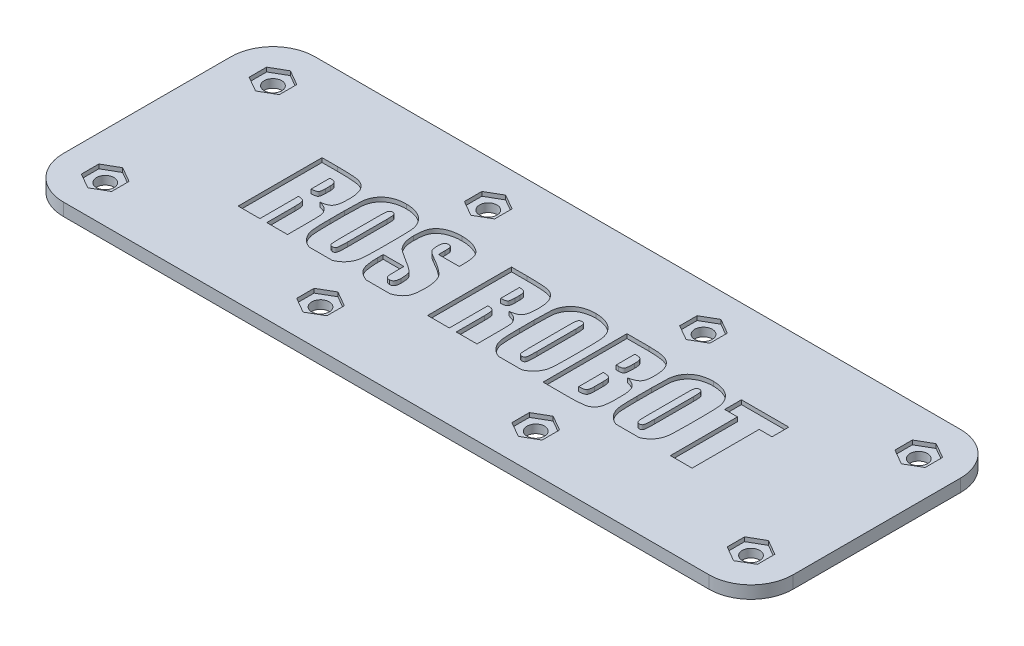
SolidWorks part; units mm, degrees
ref_plane "Front Plane" through (0, 0, 0) normal (0, 0, 1) x (1, 0, 0)
ref_plane "Top Plane" through (0, 0, 0) normal (0, 1, 0) x (1, 0, 0)
ref_plane "Right Plane" through (0, 0, 0) normal (1, 0, 0) x (0, 0, -1)
sketch "Sketch1" plane through (0, 0, 0) normal (0, 1, 0) x (1, 0, 0)
  line L1 (-87, 30) -> (87, 30)
  line L2 (-87, 30) -> (-87, -30)
  line L3 (-87, -30) -> (87, -30)
  line L4 (87, 30) -> (87, -30)
  line L5 (-87, 30) -> (87, -30) construction
  line L6 (-87, -30) -> (87, 30) construction
  point P0 (0, 0)
  dimension "D1" = 60
  dimension "D2" = 174
extrude "Boss-Extrude1" add sketch "Sketch1" along normal blind 3
sketch "Sketch2" plane through (0, 3, 0) normal (0, 1, 0) x (1, 0, 0)
  line L0 (-87, 30) -> (-87, -30) construction
  circle A0 centre (-76.995, 20) radius 2.09
  circle A1 centre (-25.665, 20) radius 2.09
  circle A2 centre (25.665, 20) radius 2.09
  circle A3 centre (76.995, 20) radius 2.09
  dimension "D1" = 4.18
  dimension "D2" = 4
  dimension "D3" = 10.005
  dimension "D4" = 20
extrude "Cut-Extrude1" cut sketch "Sketch2" against normal through all
mirror "Mirror1" about plane through (0, 0, 0) normal (0, 0, 1) of "Cut-Extrude1"
fillet "Fillet1" radius 10 4 edges at (-87, 1.5, 30) (87, 1.5, 30) (87, 1.5, -30) (-87, 1.5, -30)
sketch "Sketch3" plane through (0, 3, 0) normal (0, 1, 0) x (1, 0, 0)
  line L0 (-70, -10) -> (70, -10)
  line L1 (-55.2941, 10) -> (-51.5662, 10)
  line L2 (-43.5294, -4.6581) -> (-43.5294, -10)
  line L3 (-43.5294, -10) -> (-48.4706, -10)
  line L4 (-48.4706, -10) -> (-48.4706, -3.2353)
  line L5 (-50.1176, -0.8235) -> (-50.1176, -10)
  line L6 (-50.1176, -10) -> (-55.2941, -10)
  line L7 (-55.2941, -10) -> (-55.2941, 10)
  line L8 (-50.1176, 6.7059) -> (-50.1176, 2.2353)
  line L9 (-48.4706, 4.0478) -> (-48.4706, 5.1544)
  line L10 (-41.6471, -1.7206) -> (-41.6471, 1.7206)
  line L11 (-29.6471, 1.7206) -> (-29.6471, -1.7206)
  line L12 (-36.4706, 4.9596) -> (-36.4706, -4.5662)
  line L13 (-34.8235, -4.4154) -> (-34.8235, 4.9596)
  line L14 (-16.4706, 3.8824) -> (-21.4118, 3.8824)
  line L15 (-21.4118, 3.8824) -> (-21.4118, 5.4632)
  line L16 (-28, -4.0478) -> (-28, -2.7059)
  line L17 (-28, -2.7059) -> (-23.0588, -2.7059)
  line L18 (-23.0588, -2.7059) -> (-23.0588, -5.2978)
  line L19 (-16.4706, 4.6875) -> (-16.4706, 3.8824)
  line L20 (-10.1176, 10) -> (-6.3897, 10)
  line L21 (1.6471, -4.6581) -> (1.6471, -10)
  line L22 (1.6471, -10) -> (-3.2941, -10)
  line L23 (-3.2941, -10) -> (-3.2941, -3.2353)
  line L24 (-4.9412, -0.8235) -> (-4.9412, -10)
  line L25 (-4.9412, -10) -> (-10.1176, -10)
  line L26 (-10.1176, -10) -> (-10.1176, 10)
  line L27 (-4.9412, 6.7059) -> (-4.9412, 2.2353)
  line L28 (-3.2941, 4.0478) -> (-3.2941, 5.1544)
  line L29 (3.5294, -1.7206) -> (3.5294, 1.7206)
  line L30 (15.5294, 1.7206) -> (15.5294, -1.7206)
  line L31 (8.7059, 4.9596) -> (8.7059, -4.5662)
  line L32 (10.3529, -4.4154) -> (10.3529, 4.9596)
  line L33 (17.4118, 10) -> (22.7169, 10)
  line L34 (29.6471, -3.364) -> (29.6471, -5.2426)
  line L35 (23.4926, -10) -> (17.4118, -10)
  line L36 (17.4118, -10) -> (17.4118, 10)
  line L37 (22.5882, 6.7059) -> (22.5882, 2.2353)
  line L38 (22.5882, -0.8235) -> (22.5882, -6.7059)
  line L39 (24.4706, -4.7463) -> (24.4706, -2.7831)
  line L40 (31.5294, -1.7206) -> (31.5294, 1.7206)
  line L41 (43.5294, 1.7206) -> (43.5294, -1.7206)
  line L42 (36.7059, 4.9596) -> (36.7059, -4.5662)
  line L43 (38.3529, -4.4154) -> (38.3529, 4.9596)
  line L44 (56, 10) -> (56, 6)
  line L45 (56, 6) -> (52.9412, 6)
  line L46 (52.9412, 6) -> (52.9412, -10)
  line L47 (52.9412, -10) -> (47.7647, -10)
  line L48 (47.7647, -10) -> (47.7647, 6)
  line L49 (47.7647, 6) -> (44.7059, 6)
  line L50 (44.7059, 6) -> (44.7059, 10)
  line L51 (44.7059, 10) -> (56, 10)
  spline S0 degree 3 poles (-51.5662, 10) (-50.9938, 10.0021) (-50.1738, 9.9925) (-49.131, 9.9618) (-48.4616, 9.9343) (-47.8671, 9.8938) (-47.3485, 9.8469) (-46.9053, 9.7938) (-46.5265, 9.7279) (-46.1927, 9.6422) (-45.8846, 9.5296) (-45.5898, 9.3956) (-45.3117, 9.2282) (-45.0523, 9.0316) (-44.8023, 8.8156) (-44.5748, 8.5646) (-44.3559, 8.2904) (-44.158, 7.9777) (-43.9907, 7.6226) (-43.847, 7.2263) (-43.7305, 6.7869) (-43.6403, 6.3051) (-43.5478, 5.579) (-43.5348, 5.0099) (-43.5294, 4.6176) knots 0 0 0 0 0.148881 0.213303 0.271377 0.323138 0.368276 0.406827 0.439217 0.468212 0.496346 0.524443 0.552325 0.580569 0.609028 0.638128 0.668547 0.700209 0.734143 0.770448 0.80973 0.852244 0.897872 1 1 1 1
  spline S1 degree 3 poles (-43.5294, 4.6176) (-43.5236, 4.2653) (-43.5474, 3.7599) (-43.6025, 3.1182) (-43.671, 2.7076) (-43.7489, 2.3431) (-43.8469, 2.023) (-43.9667, 1.7514) (-44.1058, 1.5209) (-44.2744, 1.3269) (-44.4747, 1.1564) (-44.7132, 1.0108) (-44.9842, 0.8814) (-45.2896, 0.7718) (-45.7649, 0.6509) (-46.1435, 0.5949) (-46.4081, 0.5735) knots 0 0 0 0 0.18379 0.264137 0.336087 0.400976 0.458649 0.510492 0.555595 0.598692 0.64408 0.692369 0.744168 0.800637 0.861472 1 1 1 1
  spline S2 degree 3 poles (-46.4081, 0.5735) (-46.1692, 0.5082) (-45.8228, 0.4157) (-45.3924, 0.2537) (-45.1176, 0.1239) (-44.8709, -0.0075) (-44.6579, -0.1504) (-44.475, -0.3016) (-44.2801, -0.5089) (-44.0843, -0.7699) (-43.8891, -1.0747) (-43.748, -1.3697) (-43.6652, -1.6199) (-43.6287, -1.8463) (-43.5978, -2.0715) (-43.5791, -2.3577) (-43.5604, -2.7033) (-43.5466, -3.1078) (-43.5296, -3.7658) (-43.5348, -4.2893) (-43.5294, -4.6581) knots 0 0 0 0 0.11023 0.159227 0.204341 0.24532 0.283418 0.318243 0.350629 0.40972 0.463107 0.511383 0.554826 0.57974 0.613275 0.655917 0.707227 0.767226 0.835926 1 1 1 1
  spline S3 degree 3 poles (-48.4706, -3.2353) (-48.4728, -2.9891) (-48.4724, -2.639) (-48.5052, -2.1981) (-48.5325, -1.9256) (-48.5697, -1.6913) (-48.6105, -1.4957) (-48.6657, -1.339) (-48.7289, -1.2146) (-48.8113, -1.114) (-48.9232, -1.039) (-49.055, -0.9678) (-49.2166, -0.9133) (-49.4044, -0.8752) (-49.7069, -0.834) (-49.9484, -0.8249) (-50.1176, -0.8235) knots 0 0 0 0 0.208712 0.296135 0.374434 0.440653 0.497065 0.543362 0.580978 0.614872 0.652041 0.694298 0.741574 0.795735 0.856514 1 1 1 1
  spline S4 degree 3 poles (-50.1176, 2.2353) (-49.8576, 2.2338) (-49.4959, 2.2542) (-49.0697, 2.3585) (-48.8674, 2.4456) (-48.7457, 2.5571) (-48.6674, 2.6702) (-48.6082, 2.8204) (-48.5571, 3.0015) (-48.5182, 3.2158) (-48.4758, 3.5672) (-48.4762, 3.8494) (-48.4706, 4.0478) knots 0 0 0 0 0.26319 0.361521 0.442778 0.481273 0.526535 0.580255 0.643242 0.716208 0.799609 1 1 1 1
  spline S5 degree 3 poles (-48.4706, 5.1544) (-48.4732, 5.4183) (-48.4915, 5.7882) (-48.649, 6.209) (-48.8134, 6.422) (-49.0502, 6.5523) (-49.4796, 6.6913) (-49.8538, 6.7008) (-50.1176, 6.7059) knots 0 0 0 0 0.296724 0.405999 0.497474 0.590179 0.702697 1 1 1 1
  spline S6 degree 3 poles (-29.6471, -1.7206) (-29.6515, -2.1875) (-29.649, -2.8616) (-29.6628, -3.7232) (-29.6839, -4.2868) (-29.699, -4.7944) (-29.7259, -5.2478) (-29.7546, -5.6462) (-29.7961, -6.1016) (-29.8819, -6.6249) (-30.0686, -7.2195) (-30.3331, -7.7852) (-30.6652, -8.3214) (-31.0707, -8.8126) (-31.5464, -9.2461) (-32.0877, -9.6199) (-32.694, -9.9286) (-33.3578, -10.1686) (-34.3389, -10.4147) (-35.1174, -10.4641) (-35.6471, -10.4706) knots 0 0 0 0 0.112809 0.162854 0.208179 0.249065 0.285542 0.317902 0.345566 0.396043 0.445676 0.495616 0.546553 0.597656 0.649001 0.701564 0.75612 0.812885 0.871769 1 1 1 1
  spline S7 degree 3 poles (-35.6471, -10.4706) (-36.157, -10.4718) (-36.9063, -10.4086) (-37.8652, -10.1914) (-38.5237, -9.9594) (-39.1336, -9.6653) (-39.6789, -9.2941) (-40.1716, -8.8683) (-40.5862, -8.3693) (-40.9353, -7.8326) (-41.2061, -7.2648) (-41.3995, -6.6755) (-41.4957, -6.1587) (-41.5357, -5.7074) (-41.565, -5.3091) (-41.59, -4.8519) (-41.6129, -4.3384) (-41.6259, -3.766) (-41.6415, -2.8873) (-41.6458, -2.1985) (-41.6471, -1.7206) knots 0 0 0 0 0.123179 0.180929 0.237119 0.291548 0.344027 0.396062 0.448383 0.50021 0.550408 0.599943 0.649656 0.677029 0.709392 0.746168 0.787661 0.833574 0.884513 1 1 1 1
  spline S8 degree 3 poles (-41.6471, 1.7206) (-41.6425, 2.1887) (-41.6454, 2.8628) (-41.6311, 3.7244) (-41.6108, 4.2868) (-41.5934, 4.7954) (-41.5734, 5.2491) (-41.5426, 5.6473) (-41.5025, 6.102) (-41.4109, 6.6245) (-41.2257, 7.2194) (-40.9622, 7.7848) (-40.6264, 8.3182) (-40.225, 8.8141) (-39.7442, 9.2434) (-39.2063, 9.6217) (-38.599, 9.9269) (-37.9368, 10.1755) (-36.9518, 10.4071) (-36.1771, 10.476) (-35.6471, 10.4706) knots 0 0 0 0 0.1131 0.162847 0.20817 0.249054 0.28581 0.317873 0.345536 0.396062 0.445693 0.495631 0.546315 0.597643 0.649205 0.701523 0.756077 0.812942 0.872041 1 1 1 1
  spline S9 degree 3 poles (-35.6471, 10.4706) (-35.1376, 10.4697) (-34.3878, 10.4128) (-33.4319, 10.1862) (-32.7748, 9.9554) (-32.1629, 9.6647) (-31.6159, 9.2964) (-31.1263, 8.8668) (-30.7111, 8.3696) (-30.3634, 7.8316) (-30.0871, 7.2658) (-29.8946, 6.6743) (-29.798, 6.1563) (-29.7599, 5.7048) (-29.7225, 5.3082) (-29.7063, 4.8517) (-29.6803, 4.3385) (-29.6698, 3.7659) (-29.6434, 2.8875) (-29.6546, 2.1984) (-29.6471, 1.7206) knots 0 0 0 0 0.123202 0.180743 0.236944 0.291253 0.343988 0.395811 0.448142 0.499979 0.550314 0.59986 0.649873 0.677251 0.709348 0.746116 0.787617 0.833538 0.884493 1 1 1 1
  spline S10 degree 3 poles (-34.8235, 4.9596) (-34.8242, 5.1753) (-34.83, 5.4829) (-34.843, 5.8716) (-34.8622, 6.1155) (-34.8839, 6.3276) (-34.9074, 6.5086) (-34.9406, 6.6559) (-34.9862, 6.806) (-35.0702, 6.954) (-35.2687, 7.1431) (-35.486, 7.1725) (-35.6213, 7.1765) knots 0 0 0 0 0.245382 0.350014 0.44228 0.523563 0.592561 0.649714 0.69512 0.770679 0.840726 1 1 1 1
  spline S11 degree 3 poles (-35.6213, 7.1765) (-35.7476, 7.1828) (-35.9326, 7.1386) (-36.1407, 7.0007) (-36.2446, 6.8771) (-36.3135, 6.7446) (-36.354, 6.6034) (-36.3908, 6.4253) (-36.4175, 6.2075) (-36.4453, 5.9516) (-36.4612, 5.5307) (-36.473, 5.1963) (-36.4706, 4.9596) knots 0 0 0 0 0.141273 0.207934 0.278501 0.320511 0.375555 0.443281 0.525523 0.622695 0.733336 1 1 1 1
  spline S12 degree 3 poles (-36.4706, -4.5662) (-36.4661, -4.8346) (-36.4689, -5.2158) (-36.4552, -5.6951) (-36.4341, -5.9902) (-36.4194, -6.2432) (-36.3928, -6.4541) (-36.365, -6.6225) (-36.3252, -6.7864) (-36.2427, -6.9456) (-36.032, -7.1431) (-35.8027, -7.1757) (-35.6581, -7.1765) knots 0 0 0 0 0.263966 0.37491 0.47152 0.554902 0.624119 0.680394 0.722784 0.789642 0.853612 1 1 1 1
  spline S13 degree 3 poles (-35.6581, -7.1765) (-35.5065, -7.1791) (-35.2706, -7.1295) (-35.0575, -6.9077) (-34.9787, -6.7275) (-34.9317, -6.5458) (-34.9057, -6.3632) (-34.8796, -6.1401) (-34.8574, -5.8753) (-34.8447, -5.5687) (-34.8286, -5.0773) (-34.825, -4.6887) (-34.8235, -4.4154) knots 0 0 0 0 0.145036 0.209347 0.281953 0.327187 0.385478 0.455017 0.538188 0.634996 0.743262 1 1 1 1
  spline S14 degree 3 poles (-21.4118, 5.4632) (-21.4127, 5.7647) (-21.4197, 6.1714) (-21.5052, 6.6431) (-21.5927, 6.8638) (-21.7193, 7.0116) (-21.938, 7.1462) (-22.1365, 7.1803) (-22.2721, 7.1765) knots 0 0 0 0 0.412843 0.553103 0.65361 0.73318 0.814494 1 1 1 1
  spline S15 degree 3 poles (-22.2721, 7.1765) (-22.4224, 7.1753) (-22.6526, 7.1339) (-22.8986, 6.9564) (-23.0494, 6.7779) (-23.1638, 6.5473) (-23.267, 6.1427) (-23.3007, 5.8109) (-23.2941, 5.5735) knots 0 0 0 0 0.212113 0.312859 0.418563 0.535756 0.66915 1 1 1 1
  spline S16 degree 3 poles (-23.2941, 5.5735) (-23.2963, 5.2685) (-23.2666, 4.7355) (-23.1434, 4.2139) (-23.0441, 4.0074) knots 0 0 0 0 0.572651 1 1 1 1
  spline S17 degree 3 poles (-23.0441, 4.0074) (-22.9953, 3.9087) (-22.892, 3.7635) (-22.7165, 3.5783) (-22.5391, 3.4317) (-22.3344, 3.2741) (-21.9996, 3.0492) (-21.7223, 2.8928) (-21.5294, 2.7831) knots 0 0 0 0 0.166753 0.269572 0.387216 0.516182 0.662459 1 1 1 1
  spline S18 degree 3 poles (-21.5294, 2.7831) (-20.9703, 2.4734) (-20.1729, 2.0184) (-19.1897, 1.3881) (-18.5738, 0.9563) (-18.0389, 0.5522) (-17.4805, 0.0677) (-17.1194, -0.3024) (-16.9375, -0.5662) knots 0 0 0 0 0.335278 0.4813 0.612364 0.729739 0.832713 1 1 1 1
  spline S19 degree 3 poles (-16.9375, -0.5662) (-16.77, -0.806) (-16.5589, -1.2115) (-16.3573, -1.8106) (-16.226, -2.3243) (-16.1237, -2.8906) (-16.0244, -3.7446) (-16, -4.4137) (-16, -4.875) knots 0 0 0 0 0.195997 0.304678 0.423526 0.551406 0.690506 1 1 1 1
  spline S20 degree 3 poles (-16, -4.875) (-15.998, -5.2123) (-16.0141, -5.701) (-16.0695, -6.3269) (-16.1225, -6.7434) (-16.1969, -7.1236) (-16.2837, -7.469) (-16.3859, -7.7809) (-16.5079, -8.061) (-16.6548, -8.3173) (-16.8301, -8.5575) (-17.0323, -8.7896) (-17.2656, -9.0103) (-17.5281, -9.2213) (-17.8225, -9.4176) (-18.1454, -9.6065) (-18.6171, -9.8482) (-19.2609, -10.0984) (-20.3935, -10.3986) (-21.2929, -10.4667) (-21.9044, -10.4706) knots 0 0 0 0 0.107307 0.155459 0.199907 0.240819 0.278648 0.313174 0.345124 0.37569 0.406967 0.439576 0.4735 0.509002 0.546638 0.58596 0.627987 0.715167 0.805112 1 1 1 1
  spline S21 degree 3 poles (-21.9044, -10.4706) (-22.2484, -10.4757) (-22.7548, -10.4446) (-23.4141, -10.3628) (-23.8804, -10.2732) (-24.328, -10.1612) (-24.7555, -10.0192) (-25.1658, -9.8605) (-25.5494, -9.6676) (-25.9093, -9.4591) (-26.2396, -9.2368) (-26.5368, -8.9991) (-26.8027, -8.7496) (-27.0363, -8.4842) (-27.2339, -8.2027) (-27.4071, -7.9126) (-27.5395, -7.5995) (-27.6487, -7.2653) (-27.7465, -6.9026) (-27.8193, -6.5061) (-27.8876, -6.0774) (-27.9373, -5.6159) (-27.9879, -4.936) (-27.9998, -4.4094) (-28, -4.0478) knots 0 0 0 0 0.100145 0.147666 0.193464 0.238409 0.281993 0.324627 0.366464 0.406944 0.445764 0.482345 0.517706 0.551866 0.585155 0.617796 0.650099 0.683973 0.720175 0.759459 0.801374 0.84664 0.894618 1 1 1 1
  spline S22 degree 3 poles (-23.0588, -5.2978) (-23.0613, -5.4794) (-23.049, -5.7378) (-23.0335, -6.0657) (-23.0047, -6.2711) (-22.98, -6.4517) (-22.9371, -6.6031) (-22.8953, -6.7301) (-22.8277, -6.8628) (-22.7117, -6.9937) (-22.4544, -7.1506) (-22.2151, -7.1729) (-22.0551, -7.1765) knots 0 0 0 0 0.221449 0.31586 0.400263 0.474516 0.538003 0.591926 0.637412 0.719013 0.801608 1 1 1 1
  spline S23 degree 3 poles (-22.0551, -7.1765) (-21.8855, -7.181) (-21.6369, -7.1297) (-21.3606, -6.9481) (-21.2049, -6.755) (-21.0818, -6.5138) (-20.9682, -6.0948) (-20.9412, -5.7502) (-20.9412, -5.5074) knots 0 0 0 0 0.223296 0.324627 0.430189 0.546596 0.679609 1 1 1 1
  spline S24 degree 3 poles (-20.9412, -5.5074) (-20.9409, -5.2301) (-20.9533, -4.8334) (-21.0013, -4.3304) (-21.0575, -4.013) (-21.1206, -3.7324) (-21.2279, -3.4321) (-21.3302, -3.2311) (-21.4228, -3.125) knots 0 0 0 0 0.336674 0.481824 0.613234 0.728042 0.830673 1 1 1 1
  spline S25 degree 3 poles (-21.4228, -3.125) (-21.528, -3.0068) (-21.7234, -2.8316) (-22.0286, -2.599) (-22.3207, -2.3816) (-22.6652, -2.1468) (-23.2182, -1.7846) (-23.6661, -1.5149) (-23.9779, -1.3235) knots 0 0 0 0 0.151175 0.250667 0.367276 0.49971 0.649705 1 1 1 1
  spline S26 degree 3 poles (-23.9779, -1.3235) (-24.2945, -1.1313) (-24.7469, -0.8536) (-25.3157, -0.487) (-25.6766, -0.2459) (-25.9964, -0.028) (-26.2707, 0.1697) (-26.5041, 0.3453) (-26.7572, 0.5568) (-27.0307, 0.8386) (-27.3222, 1.2196) (-27.5825, 1.6572) (-27.8168, 2.1499) (-28.0109, 2.7079) (-28.187, 3.5918) (-28.2419, 4.2954) (-28.2353, 4.7868) knots 0 0 0 0 0.139497 0.199929 0.25485 0.30299 0.345648 0.382207 0.412998 0.469794 0.529711 0.593278 0.661207 0.734924 0.815133 1 1 1 1
  spline S27 degree 3 poles (-28.2353, 4.7868) (-28.2299, 5.1483) (-28.2229, 5.6721) (-28.1555, 6.342) (-28.0911, 6.7866) (-28.0062, 7.1929) (-27.9063, 7.5618) (-27.7803, 7.8893) (-27.6392, 8.183) (-27.4744, 8.4486) (-27.2854, 8.6932) (-27.0793, 8.9296) (-26.8428, 9.1431) (-26.5869, 9.3479) (-26.3089, 9.5388) (-26.0053, 9.711) (-25.5665, 9.9259) (-24.9651, 10.1466) (-23.8851, 10.4114) (-23.0241, 10.4702) (-22.4338, 10.4706) knots 0 0 0 0 0.115094 0.16642 0.214115 0.25793 0.298418 0.335563 0.369391 0.401957 0.434786 0.46765 0.501588 0.535991 0.571894 0.608743 0.64693 0.727243 0.81197 1 1 1 1
  spline S28 degree 3 poles (-22.4338, 10.4706) (-22.0994, 10.4657) (-21.6053, 10.4579) (-20.9648, 10.377) (-20.5106, 10.312) (-20.0772, 10.2133) (-19.6613, 10.1018) (-19.2659, 9.965) (-18.8924, 9.8068) (-18.5432, 9.6352) (-18.2193, 9.4575) (-17.9337, 9.2583) (-17.6686, 9.0613) (-17.4461, 8.8391) (-17.2428, 8.617) (-17.0786, 8.377) (-16.9405, 8.1223) (-16.8309, 7.8384) (-16.7307, 7.5198) (-16.6529, 7.1549) (-16.5815, 6.7482) (-16.5328, 6.2949) (-16.4819, 5.6039) (-16.471, 5.0626) (-16.4706, 4.6875) knots 0 0 0 0 0.103081 0.151694 0.198641 0.244219 0.288419 0.331125 0.37288 0.413199 0.450863 0.486435 0.520313 0.552325 0.583055 0.612876 0.641566 0.672036 0.706398 0.744284 0.786764 0.83346 0.884523 1 1 1 1
  spline S29 degree 3 poles (-6.3897, 10) (-5.8173, 10.0021) (-4.9973, 9.9925) (-3.9545, 9.9618) (-3.2851, 9.9343) (-2.6907, 9.8938) (-2.172, 9.8469) (-1.7288, 9.7938) (-1.3501, 9.7279) (-1.0162, 9.6422) (-0.7081, 9.5296) (-0.4133, 9.3956) (-0.1353, 9.2282) (0.1241, 9.0316) (0.3741, 8.8156) (0.6016, 8.5646) (0.8205, 8.2904) (1.0184, 7.9777) (1.1858, 7.6226) (1.3294, 7.2263) (1.4459, 6.7869) (1.5362, 6.3051) (1.6287, 5.579) (1.6416, 5.0099) (1.6471, 4.6176) knots 0 0 0 0 0.148881 0.213303 0.271377 0.323138 0.368276 0.406827 0.439217 0.468212 0.496346 0.524443 0.552325 0.580569 0.609028 0.638128 0.668547 0.700209 0.734143 0.770448 0.80973 0.852244 0.897872 1 1 1 1
  spline S30 degree 3 poles (1.6471, 4.6176) (1.6529, 4.2653) (1.629, 3.7599) (1.574, 3.1182) (1.5054, 2.7076) (1.4275, 2.3431) (1.3296, 2.023) (1.2098, 1.7514) (1.0707, 1.5209) (0.9021, 1.3269) (0.7018, 1.1564) (0.4633, 1.0108) (0.1923, 0.8814) (-0.1131, 0.7718) (-0.5885, 0.6509) (-0.9671, 0.5949) (-1.2316, 0.5735) knots 0 0 0 0 0.18379 0.264137 0.336087 0.400976 0.458649 0.510492 0.555595 0.598692 0.64408 0.692369 0.744168 0.800637 0.861472 1 1 1 1
  spline S31 degree 3 poles (-1.2316, 0.5735) (-0.9927, 0.5082) (-0.6463, 0.4157) (-0.2159, 0.2537) (0.0589, 0.1239) (0.3056, -0.0075) (0.5186, -0.1504) (0.7015, -0.3016) (0.8963, -0.5089) (1.0921, -0.7699) (1.2873, -1.0747) (1.4284, -1.3697) (1.5113, -1.6199) (1.5478, -1.8463) (1.5787, -2.0715) (1.5973, -2.3577) (1.6161, -2.7033) (1.6298, -3.1078) (1.6469, -3.7658) (1.6416, -4.2893) (1.6471, -4.6581) knots 0 0 0 0 0.11023 0.159227 0.204341 0.24532 0.283418 0.318243 0.350629 0.40972 0.463107 0.511383 0.554826 0.57974 0.613275 0.655917 0.707227 0.767226 0.835926 1 1 1 1
  spline S32 degree 3 poles (-3.2941, -3.2353) (-3.2963, -2.9891) (-3.2959, -2.639) (-3.3287, -2.1981) (-3.356, -1.9256) (-3.3932, -1.6913) (-3.434, -1.4957) (-3.4893, -1.339) (-3.5525, -1.2146) (-3.6348, -1.114) (-3.7468, -1.039) (-3.8785, -0.9678) (-4.0401, -0.9133) (-4.2279, -0.8752) (-4.5304, -0.834) (-4.7719, -0.8249) (-4.9412, -0.8235) knots 0 0 0 0 0.208712 0.296135 0.374434 0.440653 0.497065 0.543362 0.580978 0.614872 0.652041 0.694298 0.741574 0.795735 0.856514 1 1 1 1
  spline S33 degree 3 poles (-4.9412, 2.2353) (-4.6811, 2.2338) (-4.3195, 2.2542) (-3.8932, 2.3585) (-3.691, 2.4456) (-3.5692, 2.5571) (-3.491, 2.6702) (-3.4317, 2.8204) (-3.3807, 3.0015) (-3.3417, 3.2158) (-3.2993, 3.5672) (-3.2997, 3.8494) (-3.2941, 4.0478) knots 0 0 0 0 0.26319 0.361521 0.442778 0.481273 0.526535 0.580255 0.643242 0.716208 0.799609 1 1 1 1
  spline S34 degree 3 poles (-3.2941, 5.1544) (-3.2968, 5.4183) (-3.315, 5.7882) (-3.4725, 6.209) (-3.6369, 6.422) (-3.8737, 6.5523) (-4.3032, 6.6913) (-4.6773, 6.7008) (-4.9412, 6.7059) knots 0 0 0 0 0.296724 0.405999 0.497474 0.590179 0.702697 1 1 1 1
  spline S35 degree 3 poles (15.5294, -1.7206) (15.525, -2.1875) (15.5275, -2.8616) (15.5137, -3.7232) (15.4926, -4.2868) (15.4774, -4.7944) (15.4505, -5.2478) (15.4219, -5.6462) (15.3803, -6.1016) (15.2945, -6.6249) (15.1079, -7.2195) (14.8434, -7.7852) (14.5113, -8.3214) (14.1058, -8.8126) (13.6301, -9.2461) (13.0887, -9.6199) (12.4825, -9.9286) (11.8187, -10.1686) (10.8375, -10.4147) (10.059, -10.4641) (9.5294, -10.4706) knots 0 0 0 0 0.112809 0.162854 0.208179 0.249065 0.285542 0.317902 0.345566 0.396043 0.445676 0.495616 0.546553 0.597656 0.649001 0.701564 0.75612 0.812885 0.871769 1 1 1 1
  spline S36 degree 3 poles (9.5294, -10.4706) (9.0194, -10.4718) (8.2702, -10.4086) (7.3112, -10.1914) (6.6527, -9.9594) (6.0428, -9.6653) (5.4976, -9.2941) (5.0048, -8.8683) (4.5902, -8.3693) (4.2412, -7.8326) (3.9703, -7.2648) (3.777, -6.6755) (3.6808, -6.1587) (3.6408, -5.7074) (3.6114, -5.3091) (3.5864, -4.8519) (3.5636, -4.3384) (3.5505, -3.766) (3.535, -2.8873) (3.5307, -2.1985) (3.5294, -1.7206) knots 0 0 0 0 0.123179 0.180929 0.237119 0.291548 0.344027 0.396062 0.448383 0.50021 0.550408 0.599943 0.649656 0.677029 0.709392 0.746168 0.787661 0.833574 0.884513 1 1 1 1
  spline S37 degree 3 poles (3.5294, 1.7206) (3.534, 2.1887) (3.5311, 2.8628) (3.5454, 3.7244) (3.5657, 4.2868) (3.5831, 4.7954) (3.6031, 5.2491) (3.6338, 5.6473) (3.674, 6.102) (3.7656, 6.6245) (3.9507, 7.2194) (4.2143, 7.7848) (4.5501, 8.3182) (4.9514, 8.8141) (5.4322, 9.2434) (5.9701, 9.6217) (6.5774, 9.9269) (7.2397, 10.1755) (8.2247, 10.4071) (8.9993, 10.476) (9.5294, 10.4706) knots 0 0 0 0 0.1131 0.162847 0.20817 0.249054 0.28581 0.317873 0.345536 0.396062 0.445693 0.495631 0.546315 0.597643 0.649205 0.701523 0.756077 0.812942 0.872041 1 1 1 1
  spline S38 degree 3 poles (9.5294, 10.4706) (10.0389, 10.4697) (10.7887, 10.4128) (11.7445, 10.1862) (12.4016, 9.9554) (13.0135, 9.6647) (13.5606, 9.2964) (14.0502, 8.8668) (14.4654, 8.3696) (14.813, 7.8316) (15.0894, 7.2658) (15.2819, 6.6743) (15.3785, 6.1563) (15.4166, 5.7048) (15.4539, 5.3082) (15.4702, 4.8517) (15.4962, 4.3385) (15.5067, 3.7659) (15.5331, 2.8875) (15.5218, 2.1984) (15.5294, 1.7206) knots 0 0 0 0 0.123202 0.180743 0.236944 0.291253 0.343988 0.395811 0.448142 0.499979 0.550314 0.59986 0.649873 0.677251 0.709348 0.746116 0.787617 0.833538 0.884493 1 1 1 1
  spline S39 degree 3 poles (10.3529, 4.9596) (10.3523, 5.1753) (10.3464, 5.4829) (10.3334, 5.8716) (10.3143, 6.1155) (10.2926, 6.3276) (10.2691, 6.5086) (10.2359, 6.6559) (10.1902, 6.806) (10.1063, 6.954) (9.9078, 7.1431) (9.6905, 7.1725) (9.5551, 7.1765) knots 0 0 0 0 0.245382 0.350014 0.44228 0.523563 0.592561 0.649714 0.69512 0.770679 0.840726 1 1 1 1
  spline S40 degree 3 poles (9.5551, 7.1765) (9.4289, 7.1828) (9.2439, 7.1386) (9.0358, 7.0007) (8.9319, 6.8771) (8.8629, 6.7446) (8.8225, 6.6034) (8.7856, 6.4253) (8.759, 6.2075) (8.7312, 5.9516) (8.7153, 5.5307) (8.7035, 5.1963) (8.7059, 4.9596) knots 0 0 0 0 0.141273 0.207934 0.278501 0.320511 0.375555 0.443281 0.525523 0.622695 0.733336 1 1 1 1
  spline S41 degree 3 poles (8.7059, -4.5662) (8.7104, -4.8346) (8.7076, -5.2158) (8.7213, -5.6951) (8.7424, -5.9902) (8.7571, -6.2432) (8.7836, -6.4541) (8.8115, -6.6225) (8.8513, -6.7864) (8.9338, -6.9456) (9.1444, -7.1431) (9.3737, -7.1757) (9.5184, -7.1765) knots 0 0 0 0 0.263966 0.37491 0.47152 0.554902 0.624119 0.680394 0.722784 0.789642 0.853612 1 1 1 1
  spline S42 degree 3 poles (9.5184, -7.1765) (9.67, -7.1791) (9.9059, -7.1295) (10.119, -6.9077) (10.1978, -6.7275) (10.2447, -6.5458) (10.2708, -6.3632) (10.2969, -6.1401) (10.3191, -5.8753) (10.3318, -5.5687) (10.3479, -5.0773) (10.3515, -4.6887) (10.3529, -4.4154) knots 0 0 0 0 0.145036 0.209347 0.281953 0.327187 0.385478 0.455017 0.538188 0.634996 0.743262 1 1 1 1
  spline S43 degree 3 poles (22.7169, 10) (23.1103, 9.9955) (23.6819, 9.992) (24.4186, 9.9528) (24.9135, 9.9067) (25.3715, 9.8584) (25.7907, 9.7913) (26.1725, 9.7153) (26.5208, 9.6275) (26.8415, 9.5191) (27.1442, 9.3918) (27.4293, 9.2357) (27.6976, 9.0546) (27.9533, 8.8518) (28.1917, 8.6239) (28.4138, 8.3713) (28.6217, 8.094) (28.8126, 7.7825) (28.9734, 7.4264) (29.1074, 7.0267) (29.2229, 6.585) (29.3034, 6.0986) (29.3903, 5.3654) (29.4157, 4.791) (29.4118, 4.3934) knots 0 0 0 0 0.114402 0.166148 0.214441 0.258906 0.30003 0.337835 0.372059 0.404398 0.436167 0.46742 0.498748 0.530189 0.562197 0.59451 0.627862 0.662878 0.700507 0.741185 0.785348 0.833091 0.884404 1 1 1 1
  spline S44 degree 3 poles (29.4118, 4.3934) (29.4161, 4.127) (29.3961, 3.7432) (29.3352, 3.256) (29.279, 2.9367) (29.198, 2.6518) (29.1026, 2.3974) (28.9897, 2.1753) (28.854, 1.9816) (28.6904, 1.8122) (28.4956, 1.657) (28.2693, 1.5108) (28.006, 1.3797) (27.7137, 1.2484) (27.2525, 1.0966) (26.8888, 0.9936) (26.6324, 0.9412) knots 0 0 0 0 0.159593 0.229912 0.29415 0.353664 0.407126 0.456721 0.502563 0.548271 0.597357 0.65154 0.709345 0.77347 0.843372 1 1 1 1
  spline S45 degree 3 poles (26.6324, 0.9412) (26.9064, 0.8784) (27.3007, 0.7657) (27.7877, 0.563) (28.1067, 0.4024) (28.3887, 0.221) (28.6354, 0.0228) (28.849, -0.1912) (29.0238, -0.4284) (29.1732, -0.6877) (29.3023, -0.9756) (29.4066, -1.2968) (29.4955, -1.6492) (29.5643, -2.0325) (29.6289, -2.6073) (29.6457, -3.0548) (29.6471, -3.364) knots 0 0 0 0 0.144065 0.209342 0.269975 0.326732 0.380744 0.431785 0.481119 0.531179 0.584839 0.642399 0.7039 0.770874 0.841644 1 1 1 1
  spline S46 degree 3 poles (29.6471, -5.2426) (29.6469, -5.5627) (29.635, -6.0268) (29.585, -6.6223) (29.5342, -7.0199) (29.4687, -7.3845) (29.3885, -7.7163) (29.2938, -8.0154) (29.1496, -8.3632) (28.9276, -8.7469) (28.5806, -9.1307) (28.1655, -9.4378) (27.7574, -9.6247) (27.3756, -9.7329) (27.0179, -9.8055) (26.5945, -9.8667) (26.1022, -9.9115) (25.5458, -9.9523) (24.6684, -9.994) (23.9767, -9.9946) (23.4926, -10) knots 0 0 0 0 0.10225 0.148225 0.190863 0.23026 0.266534 0.299842 0.330381 0.386718 0.440498 0.49453 0.550588 0.582802 0.621196 0.667098 0.719418 0.779086 0.845327 1 1 1 1
  spline S47 degree 2 poles (22.5882, 2.2353) (22.875, 2.243) (23.1618, 2.2463) knots 0 0 0 1 1 1
  spline S48 degree 3 poles (23.1618, 2.2463) (23.394, 2.2431) (23.7204, 2.2711) (24.0836, 2.4402) (24.2309, 2.5926) (24.3018, 2.7538) (24.3482, 2.9156) (24.3821, 3.1219) (24.4157, 3.3706) (24.4401, 3.6651) (24.4654, 4.1442) (24.4705, 4.5257) (24.4706, 4.7941) knots 0 0 0 0 0.207123 0.283932 0.350841 0.389257 0.439129 0.499893 0.574453 0.661745 0.761896 1 1 1 1
  spline S49 degree 3 poles (24.4706, 4.7941) (24.4725, 5.0632) (24.4561, 5.4327) (24.3771, 5.876) (24.291, 6.1089) (24.1851, 6.2879) (24.0656, 6.4274) (23.9321, 6.5346) (23.7711, 6.6046) (23.5692, 6.647) (23.172, 6.6936) (22.8358, 6.7017) (22.5882, 6.7059) knots 0 0 0 0 0.247893 0.340016 0.413628 0.475403 0.53064 0.582138 0.631667 0.690827 0.771639 1 1 1 1
  spline S50 degree 3 poles (22.5882, -6.7059) (22.7721, -6.6974) (23.0359, -6.6865) (23.3661, -6.639) (23.5743, -6.6004) (23.7547, -6.5485) (23.9092, -6.4911) (24.0376, -6.4263) (24.1395, -6.3453) (24.2198, -6.2425) (24.2905, -6.117) (24.343, -5.9579) (24.3904, -5.7726) (24.4267, -5.5574) (24.4604, -5.2128) (24.4753, -4.9391) (24.4706, -4.7463) knots 0 0 0 0 0.168587 0.241054 0.305045 0.362185 0.41258 0.455716 0.49319 0.530665 0.574337 0.624343 0.683356 0.749349 0.823768 1 1 1 1
  spline S51 degree 3 poles (24.4706, -2.7831) (24.4699, -2.581) (24.4683, -2.2928) (24.427, -1.9325) (24.4043, -1.7098) (24.3567, -1.5228) (24.3088, -1.3668) (24.2464, -1.244) (24.1737, -1.147) (24.0747, -1.0775) (23.9541, -1.0154) (23.7998, -0.9656) (23.6165, -0.9226) (23.4028, -0.8865) (23.0575, -0.8455) (22.7821, -0.8306) (22.5882, -0.8235) knots 0 0 0 0 0.18245 0.259089 0.327073 0.383894 0.432816 0.473837 0.507662 0.540813 0.581834 0.629709 0.686529 0.751567 0.825033 1 1 1 1
  spline S52 degree 3 poles (43.5294, -1.7206) (43.525, -2.1875) (43.5275, -2.8616) (43.5137, -3.7232) (43.4926, -4.2868) (43.4774, -4.7944) (43.4505, -5.2478) (43.4219, -5.6462) (43.3803, -6.1016) (43.2945, -6.6249) (43.1079, -7.2195) (42.8434, -7.7852) (42.5113, -8.3214) (42.1058, -8.8126) (41.6301, -9.2461) (41.0887, -9.6199) (40.4825, -9.9286) (39.8187, -10.1686) (38.8375, -10.4147) (38.059, -10.4641) (37.5294, -10.4706) knots 0 0 0 0 0.112809 0.162854 0.208179 0.249065 0.285542 0.317902 0.345566 0.396043 0.445676 0.495616 0.546553 0.597656 0.649001 0.701564 0.75612 0.812885 0.871769 1 1 1 1
  spline S53 degree 3 poles (37.5294, -10.4706) (37.0194, -10.4718) (36.2702, -10.4086) (35.3112, -10.1914) (34.6527, -9.9594) (34.0428, -9.6653) (33.4976, -9.2941) (33.0048, -8.8683) (32.5902, -8.3693) (32.2412, -7.8326) (31.9703, -7.2648) (31.777, -6.6755) (31.6808, -6.1587) (31.6408, -5.7074) (31.6114, -5.3091) (31.5864, -4.8519) (31.5636, -4.3384) (31.5505, -3.766) (31.535, -2.8873) (31.5307, -2.1985) (31.5294, -1.7206) knots 0 0 0 0 0.123179 0.180929 0.237119 0.291548 0.344027 0.396062 0.448383 0.50021 0.550408 0.599943 0.649656 0.677029 0.709392 0.746168 0.787661 0.833574 0.884513 1 1 1 1
  spline S54 degree 3 poles (31.5294, 1.7206) (31.534, 2.1887) (31.5311, 2.8628) (31.5454, 3.7244) (31.5657, 4.2868) (31.5831, 4.7954) (31.6031, 5.2491) (31.6338, 5.6473) (31.674, 6.102) (31.7656, 6.6245) (31.9507, 7.2194) (32.2143, 7.7848) (32.5501, 8.3182) (32.9514, 8.8141) (33.4322, 9.2434) (33.9701, 9.6217) (34.5774, 9.9269) (35.2397, 10.1755) (36.2247, 10.4071) (36.9993, 10.476) (37.5294, 10.4706) knots 0 0 0 0 0.1131 0.162847 0.20817 0.249054 0.28581 0.317873 0.345536 0.396062 0.445693 0.495631 0.546315 0.597643 0.649205 0.701523 0.756077 0.812942 0.872041 1 1 1 1
  spline S55 degree 3 poles (37.5294, 10.4706) (38.0389, 10.4697) (38.7887, 10.4128) (39.7445, 10.1862) (40.4016, 9.9554) (41.0135, 9.6647) (41.5606, 9.2964) (42.0502, 8.8668) (42.4654, 8.3696) (42.813, 7.8316) (43.0894, 7.2658) (43.2819, 6.6743) (43.3785, 6.1563) (43.4166, 5.7048) (43.4539, 5.3082) (43.4702, 4.8517) (43.4962, 4.3385) (43.5067, 3.7659) (43.5331, 2.8875) (43.5218, 2.1984) (43.5294, 1.7206) knots 0 0 0 0 0.123202 0.180743 0.236944 0.291253 0.343988 0.395811 0.448142 0.499979 0.550314 0.59986 0.649873 0.677251 0.709348 0.746116 0.787617 0.833538 0.884493 1 1 1 1
  spline S56 degree 3 poles (38.3529, 4.9596) (38.3523, 5.1753) (38.3464, 5.4829) (38.3334, 5.8716) (38.3143, 6.1155) (38.2926, 6.3276) (38.2691, 6.5086) (38.2359, 6.6559) (38.1902, 6.806) (38.1063, 6.954) (37.9078, 7.1431) (37.6905, 7.1725) (37.5551, 7.1765) knots 0 0 0 0 0.245382 0.350014 0.44228 0.523563 0.592561 0.649714 0.69512 0.770679 0.840726 1 1 1 1
  spline S57 degree 3 poles (37.5551, 7.1765) (37.4289, 7.1828) (37.2439, 7.1386) (37.0358, 7.0007) (36.9319, 6.8771) (36.8629, 6.7446) (36.8225, 6.6034) (36.7856, 6.4253) (36.759, 6.2075) (36.7312, 5.9516) (36.7153, 5.5307) (36.7035, 5.1963) (36.7059, 4.9596) knots 0 0 0 0 0.141273 0.207934 0.278501 0.320511 0.375555 0.443281 0.525523 0.622695 0.733336 1 1 1 1
  spline S58 degree 3 poles (36.7059, -4.5662) (36.7104, -4.8346) (36.7076, -5.2158) (36.7213, -5.6951) (36.7424, -5.9902) (36.7571, -6.2432) (36.7836, -6.4541) (36.8115, -6.6225) (36.8513, -6.7864) (36.9338, -6.9456) (37.1444, -7.1431) (37.3737, -7.1757) (37.5184, -7.1765) knots 0 0 0 0 0.263966 0.37491 0.47152 0.554902 0.624119 0.680394 0.722784 0.789642 0.853612 1 1 1 1
  spline S59 degree 3 poles (37.5184, -7.1765) (37.67, -7.1791) (37.9059, -7.1295) (38.119, -6.9077) (38.1978, -6.7275) (38.2447, -6.5458) (38.2708, -6.3632) (38.2969, -6.1401) (38.3191, -5.8753) (38.3318, -5.5687) (38.3479, -5.0773) (38.3515, -4.6887) (38.3529, -4.4154) knots 0 0 0 0 0.145036 0.209347 0.281953 0.327187 0.385478 0.455017 0.538188 0.634996 0.743262 1 1 1 1
  point P2 (0, -10)
  dimension "D1" = 10
  dimension "D2" = 140
extrude "Cut-Extrude2" cut sketch "Sketch3" against normal blind 1 contours S3 L4 L0 L2 S2 S1 S0 L1 L7 L5 S5 L9 S4 L8 | S9 S8 L10 S7 L0 S6 L11 S13 S12 L12 S11 S10 L13 | S28 S27 S26 S25 S24 S23 S22 L18 L17 L16 S21 L0 S20 S19 S18 S17 S16 S15 S14 L15 L14 L19 | S32 L23 L0 L21 S31 S30 S29 L20 L26 L24 S34 L28 S33 L27 | S38 S37 L29 S36 L0 S35 L30 S42 S41 L31 S40 S39 L32 | S46 L34 S45 S44 S43 L33 L36 L0 S51 L39 S50 L38 S49 S48 S47 L37 | S55 S54 L40 S53 L0 S52 L41 S59 S58 L42 S57 S56 L43 | L51 L50 L49 L48 L0 L46 L45 L44 region at (-49.6197, 3, -0.0506) region at (50.3529, 3, -1.5294) region at (31.986, 3, 6.4699) region at (23.1917, 3, 0.1255) region at (3.986, 3, 6.4699) region at (-4.4432, 3, -0.0506) region at (-22.1813, 3, -0.0441) region at (-41.1905, 3, 6.4699)
sketch "Sketch4" plane through (0, 3, 0) normal (0, 1, 0) x (1, 0, 0)
  line L0 (-87, 20) -> (-87, -20) construction
  line L1 (-76.995, 15.8431) -> (-73.395, 17.9215)
  line L2 (-73.395, 17.9215) -> (-73.395, 22.0785)
  line L3 (-73.395, 22.0785) -> (-76.995, 24.1569)
  line L4 (-76.995, 24.1569) -> (-80.595, 22.0785)
  line L5 (-80.595, 22.0785) -> (-80.595, 17.9215)
  line L6 (-80.595, 17.9215) -> (-76.995, 15.8431)
  line L7 (-25.665, 15.8431) -> (-22.065, 17.9215)
  line L8 (-22.065, 17.9215) -> (-22.065, 22.0785)
  line L9 (-22.065, 22.0785) -> (-25.665, 24.1569)
  line L10 (-25.665, 24.1569) -> (-29.265, 22.0785)
  line L11 (-29.265, 22.0785) -> (-29.265, 17.9215)
  line L12 (-29.265, 17.9215) -> (-25.665, 15.8431)
  line L13 (25.665, 15.8431) -> (29.265, 17.9215)
  line L14 (29.265, 17.9215) -> (29.265, 22.0785)
  line L15 (29.265, 22.0785) -> (25.665, 24.1569)
  line L16 (25.665, 24.1569) -> (22.065, 22.0785)
  line L17 (22.065, 22.0785) -> (22.065, 17.9215)
  line L18 (22.065, 17.9215) -> (25.665, 15.8431)
  line L19 (76.995, 15.8431) -> (80.595, 17.9215)
  line L20 (80.595, 17.9215) -> (80.595, 22.0785)
  line L21 (80.595, 22.0785) -> (76.995, 24.1569)
  line L22 (76.995, 24.1569) -> (73.395, 22.0785)
  line L23 (73.395, 22.0785) -> (73.395, 17.9215)
  line L24 (73.395, 17.9215) -> (76.995, 15.8431)
  circle A0 centre (-76.995, 20) radius 3.6 construction
  circle A1 centre (-76.995, 20) radius 2.09 construction
  dimension "D1" = 7.2
  dimension "D2" = 4
extrude "Cut-Extrude3" cut sketch "Sketch4" against normal blind 1
mirror "Mirror2" about plane through (0, 0, 0) normal (0, 0, 1) of "Cut-Extrude3"
